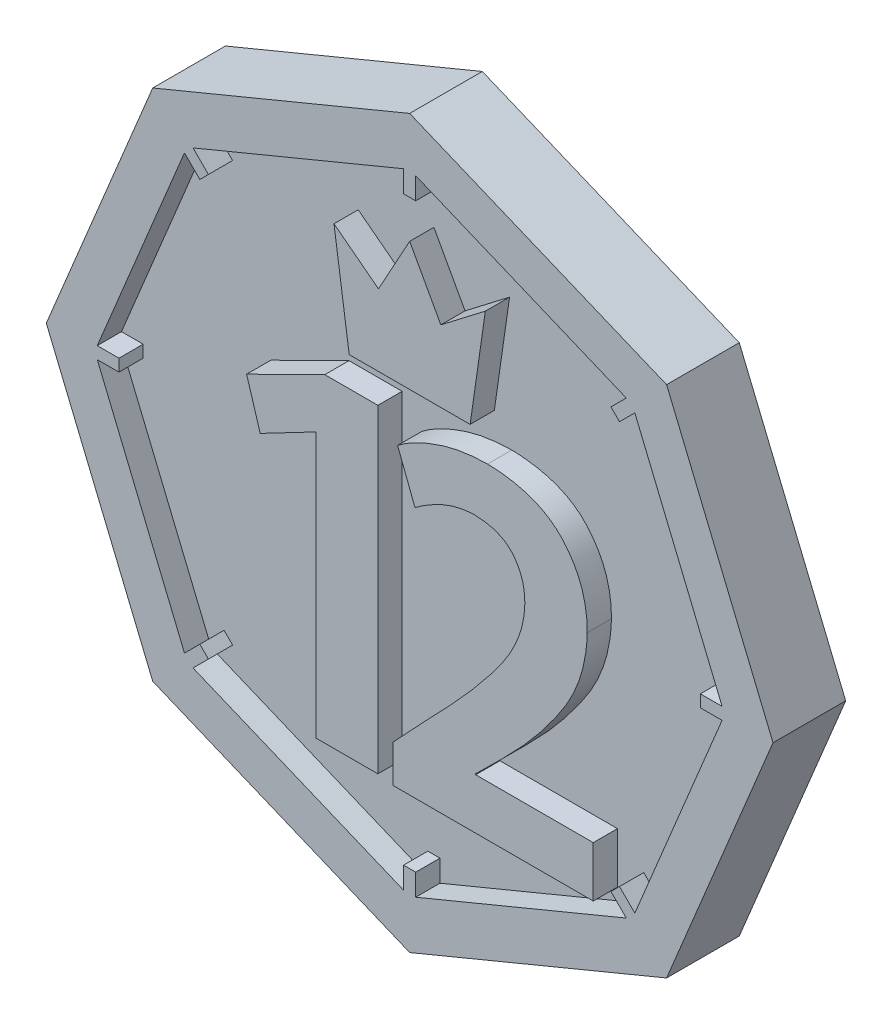
SolidWorks part; units mm, degrees
ref_plane "Front Plane" through (0, 0, 0) normal (0, 0, 1) x (1, 0, 0)
ref_plane "Top Plane" through (0, 0, 0) normal (0, 1, 0) x (1, 0, 0)
ref_plane "Right Plane" through (0, 0, 0) normal (1, 0, 0) x (0, 0, -1)
sketch "Sketch1" plane through (0, 0, 0) normal (0, 0, 1) x (1, 0, 0)
  line L0 (-26.9408, -26.9408) -> (0, -38.1)
  line L1 (38.1, 0) -> (26.9408, 26.9408)
  line L2 (26.9408, 26.9408) -> (0, 38.1)
  line L3 (0, 38.1) -> (-26.9408, 26.9408)
  line L4 (-26.9408, 26.9408) -> (-38.1, 0)
  line L5 (-38.1, 0) -> (-26.9408, -26.9408)
  line L6 (0, -38.1) -> (26.9408, -26.9408)
  line L7 (26.9408, -26.9408) -> (38.1, 0)
  line L8 (38.1, 0) -> (-38.1, 0) construction
  line L19 (33.02, 0) -> (23.3487, 23.3487)
  line L20 (23.3487, 23.3487) -> (0, 33.02)
  line L21 (0, 33.02) -> (-23.3487, 23.3487)
  line L22 (-23.3487, 23.3487) -> (-33.02, 0)
  line L23 (-33.02, 0) -> (-23.3487, -23.3487)
  line L24 (-23.3487, -23.3487) -> (0, -33.02)
  line L25 (0, -33.02) -> (23.3487, -23.3487)
  line L26 (23.3487, -23.3487) -> (33.02, 0)
  circle A0 centre (0, 0) radius 35.1998 construction
  circle A1 centre (0, 0) radius 30.5065 construction
  dimension "D1" = 76.2
  dimension "D4" = 5.08
extrude "Boss-Extrude2" add sketch "Sketch1" along normal blind 2.54 contours L25 L26 L19 L20 L21 L22 L23 L24 | L19 L20 L21 L22 L23 L24 L25 L26 region at (0, 0, 0)
extrude "Boss-Extrude3" add sketch "Sketch1<3>" along normal blind 5.08 and the other way blind 2.54 contours L6 L7 L1 L2 L3 L4 L5 L0 L26 L25 L24 L23 L22 L21 L20 L19 region at (-31.5248, -13.058, 0)
sketch "Sketch1<3>" plane through (0, 0, 0) normal (0, 0, 1) x (1, 0, 0) same geometry as "Sketch1"
sketch "Sketch2" plane through (0, 0, 2.54) normal (0, 0, 1) x (1, 0, 0)
  line L0 (-20.9874, -23.8242) -> (23.1517, -23.8242) construction
  line L1 (23.3487, -23.3487) -> (33.02, 0) construction
  line L2 (0, 33.02) -> (0, -33.02) construction
  line L3 (-6.3393, 13.0307) -> (6.3393, 13.0307)
  line L4 (6.3393, 13.0307) -> (7.935, 24.113)
  line L5 (7.935, 24.113) -> (3.2684, 20.5338)
  line L6 (3.2684, 20.5338) -> (0, 26.4848)
  line L7 (-3.2684, 20.5338) -> (0, 26.4848)
  line L8 (-7.935, 24.113) -> (-3.2684, 20.5338)
  line L9 (-6.3393, 13.0307) -> (-7.935, 24.113)
  line L20 (-23.7977, -22.8997) -> (-22.0016, -21.1036)
  line L21 (-0.635, -33.02) -> (0.635, -33.02)
  line L22 (-0.635, -33.02) -> (-0.635, -30.48)
  line L23 (-0.635, -30.48) -> (0.635, -30.48)
  line L24 (0.635, -33.02) -> (0.635, -30.48)
  line L25 (-0.635, -33.02) -> (0.635, -30.48) construction
  line L26 (-0.635, -30.48) -> (0.635, -33.02) construction
  line L27 (-23.7977, -22.8997) -> (-22.8997, -23.7977)
  line L28 (-22.8997, -23.7977) -> (-21.1036, -22.0016)
  line L29 (-22.0016, -21.1036) -> (-21.1036, -22.0016)
  line L30 (-33.02, 0.635) -> (-30.48, 0.635)
  line L31 (-33.02, 0.635) -> (-33.02, -0.635)
  line L32 (-33.02, -0.635) -> (-30.48, -0.635)
  line L33 (-30.48, 0.635) -> (-30.48, -0.635)
  line L34 (-22.8997, 23.7977) -> (-21.1036, 22.0016)
  line L35 (-22.8997, 23.7977) -> (-23.7977, 22.8997)
  line L36 (-23.7977, 22.8997) -> (-22.0016, 21.1036)
  line L37 (-21.1036, 22.0016) -> (-22.0016, 21.1036)
  line L38 (0.635, 33.02) -> (0.635, 30.48)
  line L39 (0.635, 33.02) -> (-0.635, 33.02)
  line L40 (-0.635, 33.02) -> (-0.635, 30.48)
  line L41 (0.635, 30.48) -> (-0.635, 30.48)
  line L42 (23.7977, 22.8997) -> (22.0016, 21.1036)
  line L43 (23.7977, 22.8997) -> (22.8997, 23.7977)
  line L44 (22.8997, 23.7977) -> (21.1036, 22.0016)
  line L45 (22.0016, 21.1036) -> (21.1036, 22.0016)
  line L46 (33.02, -0.635) -> (30.48, -0.635)
  line L47 (33.02, -0.635) -> (33.02, 0.635)
  line L48 (33.02, 0.635) -> (30.48, 0.635)
  line L49 (30.48, -0.635) -> (30.48, 0.635)
  line L50 (22.8997, -23.7977) -> (21.1036, -22.0016)
  line L51 (22.8997, -23.7977) -> (23.7977, -22.8997)
  line L52 (23.7977, -22.8997) -> (22.0016, -21.1036)
  line L53 (21.1036, -22.0016) -> (22.0016, -21.1036)
  circle A0 centre (0, 0) radius 31.75 construction
  text T0 "12" font "@Adobe Gothic Std B" height in points 110
  point P13 (0, 13.0307)
  point P15 (0, -31.75)
  point P24 (-24.11, -20.6584)
  point P88 (0, 0)
  dimension "D1" = 1.27
  dimension "D2" = 2.54
  dimension "D3" = 8
extrude "Boss-Extrude4" add sketch "Sketch2" along normal up to surface (2.54 mm away) up to face at (0, 0, 5.08)
sketch "Sketch4" plane through (0, 0, 0) normal (0, 0, -1) x (-1, 0, 0)
  line L0 (-25.2184, -4.9787) -> (26.1518, -4.9787) construction
  line L1 (0, -7.7987) -> (0, 16.4219) construction
  line L2 (-21.4916, -19.5056) -> (21.4916, -19.5056) construction
  line L3 (-23.3147, -7.1637) -> (-23.3147, 15.7869) construction
  line L4 (23.3147, 15.7869) -> (-23.3147, 15.7869)
  line L5 (23.3147, 15.7869) -> (23.3147, 17.0569)
  line L6 (23.3147, 17.0569) -> (-23.3147, 17.0569)
  line L7 (-23.3147, 15.7869) -> (-23.3147, 17.0569)
  line L8 (23.3147, 15.7869) -> (-23.3147, 17.0569) construction
  line L9 (23.3147, 17.0569) -> (-23.3147, 15.7869) construction
  line L10 (23.3147, -8.4337) -> (-23.3147, -8.4337)
  line L11 (23.3147, -8.4337) -> (23.3147, -7.1637)
  line L12 (23.3147, -7.1637) -> (-23.3147, -7.1637)
  line L13 (-23.3147, -8.4337) -> (-23.3147, -7.1637)
  line L14 (23.3147, -8.4337) -> (-23.3147, -7.1637) construction
  line L15 (23.3147, -7.1637) -> (-23.3147, -8.4337) construction
  line L16 (0, -7.7987) -> (0, -19.5056) construction
  line L17 (-4.4689, 18.8242) -> (4.4689, 18.8242)
  line L18 (4.4689, 18.8242) -> (5.631, 27.7386)
  line L19 (5.631, 27.7386) -> (2.0605, 23.7036)
  line L20 (2.0605, 23.7036) -> (0, 27.6821)
  line L21 (-2.0605, 23.7036) -> (0, 27.6821)
  line L22 (-5.631, 27.7386) -> (-2.0605, 23.7036)
  line L23 (-4.4689, 18.8242) -> (-5.631, 27.7386)
  line L24 (0, -33.02) -> (0, -31.75) construction
  line L25 (-0.635, -33.02) -> (0.635, -33.02)
  line L26 (-0.635, -33.02) -> (-0.635, -30.48)
  line L27 (-0.635, -30.48) -> (0.635, -30.48)
  line L28 (0.635, -33.02) -> (0.635, -30.48)
  line L29 (-0.635, -33.02) -> (0.635, -30.48) construction
  line L30 (-0.635, -30.48) -> (0.635, -33.02) construction
  line L31 (-23.7977, -22.8997) -> (-22.0016, -21.1036)
  line L32 (-23.7977, -22.8997) -> (-22.8997, -23.7977)
  line L33 (-22.8997, -23.7977) -> (-21.1036, -22.0016)
  line L34 (-22.0016, -21.1036) -> (-21.1036, -22.0016)
  line L35 (-33.02, 0.635) -> (-30.48, 0.635)
  line L36 (-33.02, 0.635) -> (-33.02, -0.635)
  line L37 (-33.02, -0.635) -> (-30.48, -0.635)
  line L38 (-30.48, 0.635) -> (-30.48, -0.635)
  line L39 (-22.8997, 23.7977) -> (-21.1036, 22.0016)
  line L40 (-22.8997, 23.7977) -> (-23.7977, 22.8997)
  line L41 (-23.7977, 22.8997) -> (-22.0016, 21.1036)
  line L42 (-21.1036, 22.0016) -> (-22.0016, 21.1036)
  line L43 (0.635, 33.02) -> (0.635, 30.48)
  line L44 (0.635, 33.02) -> (-0.635, 33.02)
  line L45 (-0.635, 33.02) -> (-0.635, 30.48)
  line L46 (0.635, 30.48) -> (-0.635, 30.48)
  line L47 (23.7977, 22.8997) -> (22.0016, 21.1036)
  line L48 (23.7977, 22.8997) -> (22.8997, 23.7977)
  line L49 (22.8997, 23.7977) -> (21.1036, 22.0016)
  line L50 (22.0016, 21.1036) -> (21.1036, 22.0016)
  line L51 (33.02, -0.635) -> (30.48, -0.635)
  line L52 (33.02, -0.635) -> (33.02, 0.635)
  line L53 (33.02, 0.635) -> (30.48, 0.635)
  line L54 (30.48, -0.635) -> (30.48, 0.635)
  line L55 (22.8997, -23.7977) -> (21.1036, -22.0016)
  line L56 (22.8997, -23.7977) -> (23.7977, -22.8997)
  line L57 (23.7977, -22.8997) -> (22.0016, -21.1036)
  line L58 (21.1036, -22.0016) -> (22.0016, -21.1036)
  circle A0 centre (0, 0.6132) radius 32.3632 construction
  text T0 "TOG" font "Bree Serif" height in points 50
  text T1 "Chapter 2" font "Bree Serif" height in points 17
  point P3 (0, -7.7987)
  point P11 (0, -31.75)
  point P12 (0, 16.4219)
  point P26 (0, 18.8242)
  point P66 (0, 0)
  dimension "D1" = 1.27
  dimension "D2" = 1.27
  dimension "D3" = 1.27
  dimension "D4" = 2.54
  dimension "D5" = 8
extrude "Boss-Extrude5" add sketch "Sketch4" along normal blind 1.27
